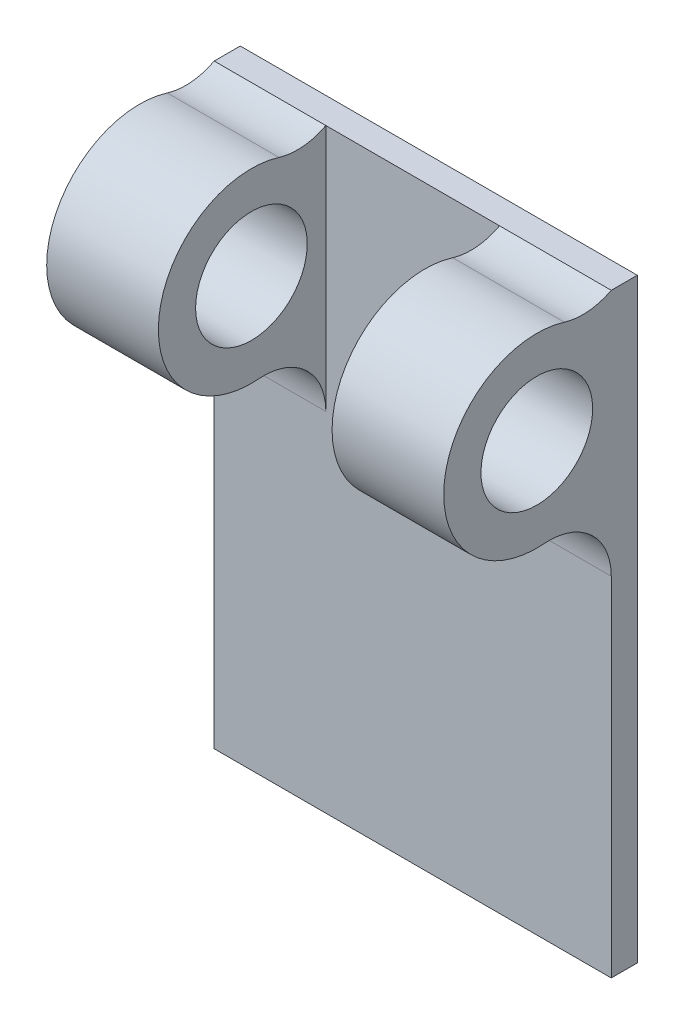
SolidWorks part; units mm, degrees
ref_plane "Front Plane" through (0, 0, 0) normal (0, 0, 1) x (1, 0, 0)
ref_plane "Top Plane" through (0, 0, 0) normal (0, 1, 0) x (1, 0, 0)
ref_plane "Right Plane" through (0, 0, 0) normal (1, 0, 0) x (0, 0, -1)
sketch "Sketch1" plane through (0, 0, 0) normal (0, 0, 1) x (1, 0, 0)
  line L1 (0, 0) -> (640, 0)
  line L2 (0, 0) -> (0, -960)
  line L3 (0, -960) -> (640, -960)
  line L4 (640, 0) -> (640, -960)
  dimension "D1" = 640
  dimension "D2" = 960
extrude "Boss-Extrude1" add sketch "Sketch1" along normal blind 42
sketch "Sketch2" plane through (0, 0, 0) normal (-1, 0, 0) x (0, 0, 1)
  line L0 (42, -150) -> (162, -150)
  line L1 (42, 0) -> (42, -960) construction
  line L2 (42, 0) -> (0, 0) construction
  circle A0 centre (162, -150) radius 150
  circle A1 centre (162, -150) radius 90
  dimension "D2" = 300
  dimension "D4" = 180
  dimension "D1" = 120
  dimension "D3" = 150
extrude "Boss-Extrude2" add sketch "Sketch2" against normal blind 640
fillet "Fillet1" radius 100 2 edges at (320, -60, 42) (320, -240, 42)
sketch "Sketch3" plane through (0, -960, 0) normal (0, -1, 0) x (1, 0, 0)
  line L0 (0, 42) -> (640, 42) construction
  line L1 (180, 42) -> (460, 42)
  line L2 (180, 42) -> (180, 373.1425)
  line L3 (180, 373.1425) -> (460, 373.1425)
  line L4 (460, 42) -> (460, 373.1425)
  line L5 (0, 150) -> (0, 42) construction
  dimension "D1" = 180
  dimension "D2" = 180
extrude "Cut-Extrude1" cut sketch "Sketch3" against normal blind 1053
